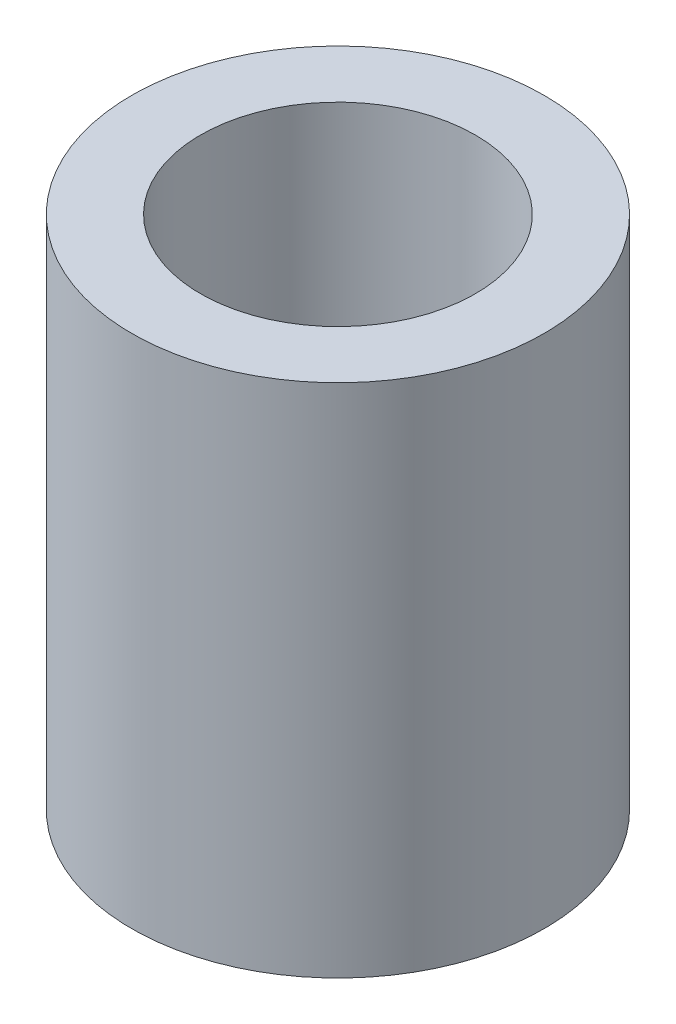
SolidWorks part; units mm, degrees
ref_plane "Front Plane" through (0, 0, 0) normal (0, 0, 1) x (1, 0, 0)
ref_plane "Top Plane" through (0, 0, 0) normal (0, 1, 0) x (1, 0, 0)
ref_plane "Right Plane" through (0, 0, 0) normal (1, 0, 0) x (0, 0, -1)
sketch "Croquis1" plane through (0, 0, 0) normal (1, 0, 0) x (0, 0, -1)
  line L0 (0, 0) -> (0, 98.0232) construction
  line L1 (16, 0) -> (24, 0)
  line L2 (16, 0) -> (16, 60)
  line L3 (16, 60) -> (24, 60)
  line L4 (24, 0) -> (24, 60)
  dimension "D2" = 8
  dimension "D3" = 60
  dimension "D1" = 48
revolve "Revolución1" add sketch "Croquis1" angle 360 about L0
equation "\"OD\"=48"
equation "\"Pared\" = 8"
equation "\"Altura\"= 60"
equation "\"D3@Croquis1\"=\"Altura\""
equation "\"D2@Croquis1\"=\"Pared\""
equation "\"D1@Croquis1\"=\"OD\""
